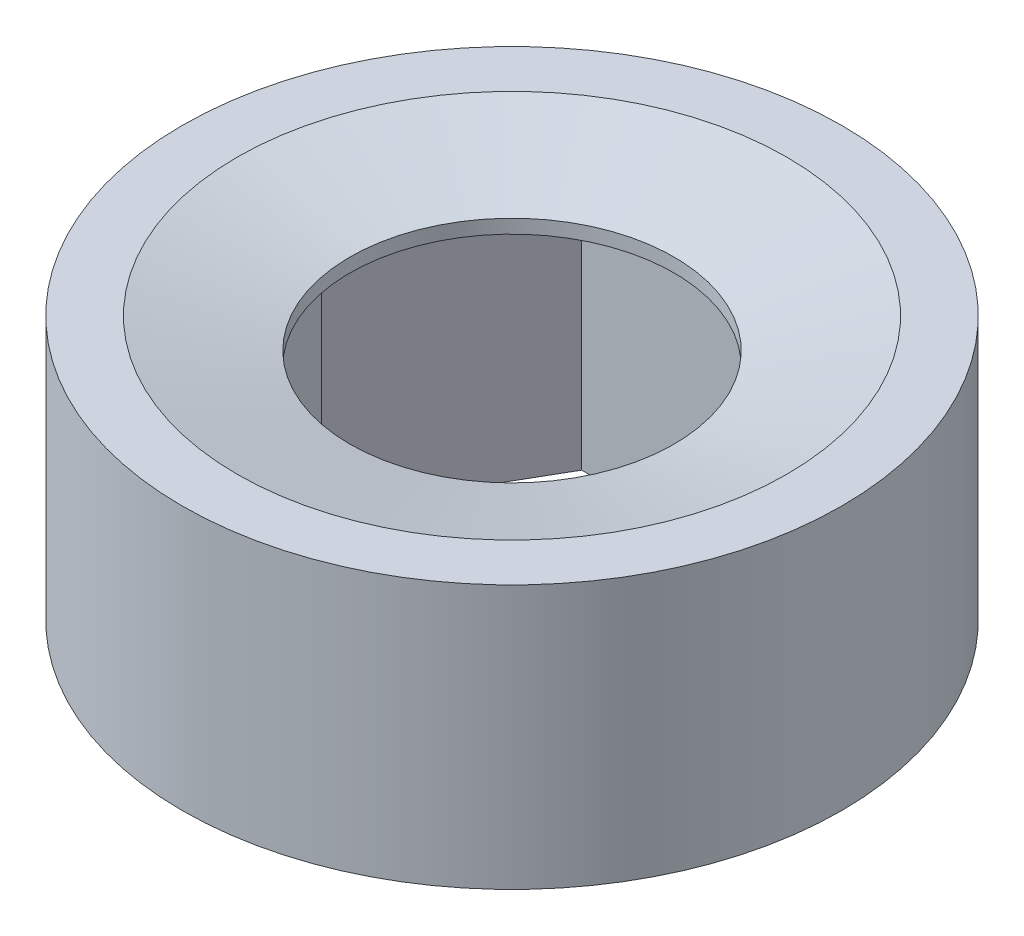
SolidWorks part; units mm, degrees
ref_plane "Front Plane" through (0, 0, 0) normal (0, 0, 1) x (1, 0, 0)
ref_plane "Top Plane" through (0, 0, 0) normal (0, 1, 0) x (1, 0, 0)
ref_plane "Right Plane" through (0, 0, 0) normal (1, 0, 0) x (0, 0, -1)
sketch "Sketch1" plane through (0, 0, 0) normal (0, 1, 0) x (1, 0, 0)
  line L0 (3.4641, 6) -> (-3.4641, 6)
  line L1 (3.4641, 6) -> (-3.4641, 6) construction
  line L2 (-3.4641, 6) -> (-6.9282, 0) construction
  line L3 (-6.9282, 0) -> (-3.4641, -6) construction
  line L4 (-3.4641, -6) -> (3.4641, -6) construction
  line L5 (3.4641, -6) -> (6.9282, 0) construction
  line L6 (6.9282, 0) -> (3.4641, 6) construction
  line L7 (-3.4641, 6) -> (-6.9282, 0)
  line L8 (-6.9282, 0) -> (-3.4641, -6)
  line L9 (-3.4641, -6) -> (3.4641, -6)
  line L10 (3.4641, -6) -> (6.9282, 0)
  line L11 (6.9282, 0) -> (3.4641, 6)
  line L13 (-10, -10) -> (10, -10) construction
  line L14 (-10, -10) -> (-10, 10) construction
  line L15 (-10, 10) -> (10, 10) construction
  line L16 (10, -10) -> (10, 10) construction
  line L17 (-10, -10) -> (10, 10) construction
  line L18 (-10, 10) -> (10, -10) construction
  circle A1 centre (0, 0) radius 6 construction
  circle A2 centre (0, 0) radius 12
  dimension "D1" = 12
  dimension "D4" = 24
  dimension "D3" = 4
  dimension "D2" = 0
extrude "Boss-Extrude1" add sketch "Sketch1" along normal blind 8
sketch "Sketch2" plane through (0, 8, 0) normal (0, 1, 0) x (1, 0, 0)
  circle A0 centre (0, 0) radius 5.9
  circle A1 centre (0, 0) radius 12
  dimension "D1" = 11.8
  dimension "D2" = 24
extrude "Boss-Extrude2" add sketch "Sketch2" along normal blind 1.6
sketch "Sketch3" plane through (0, 9.6, 0) normal (0, 1, 0) x (1, 0, 0)
  circle A1 centre (0, 0) radius 10
  dimension "D1" = 20
extrude "Cut-Extrude1" cut sketch "Sketch3" against normal blind 1.1 draft 75
sketch "Sketch6" plane through (0, 8, 0) normal (0, -1, 0) x (1, 0, 0)
  circle A0 centre (0, 0) radius 5.9
  point P4 (0, 0)
ref_axis "Axis1" through (0, 18.1877, 0) along (0, -1, 0)
equation "\"D3@Cut-Extrude1\"=90 - atn(2/5)"
